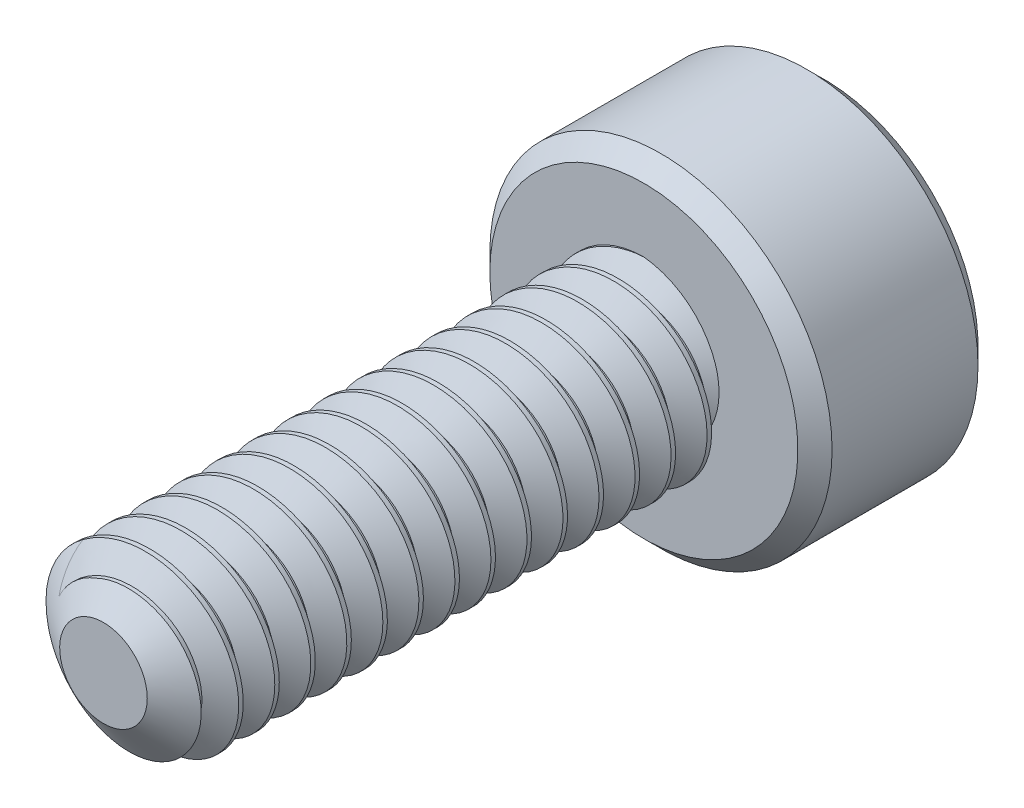
SolidWorks part; units mm, degrees
other "DetailItem1"
ref_plane "Front Plane" through (0, 0, 0) normal (0, 0, 1) x (1, 0, 0)
ref_plane "Top Plane" through (0, 0, 0) normal (0, 1, 0) x (1, 0, 0)
ref_plane "Right Plane" through (0, 0, 0) normal (1, 0, 0) x (0, 0, -1)
sketch "Sketch1" plane through (0, 0, 0) normal (0, 0, 1) x (1, 0, 0)
  circle A0 centre (0, 0) radius 1
  dimension "OD" = 2
extrude "Extrude1" add sketch "Sketch1" against normal blind 6
sketch "Sketch2" plane through (0, 0, 0) normal (0, 0, 1) x (1, 0, 0)
  circle A0 centre (0, 0) radius 1 construction
  circle A1 centre (0, 0) radius 1
curve "Helix/Spiral1" pitch 0.4 height 6.4 radius 1 centre (0, 0, 0) axis (0, 0, -1) start towards (0, 1, 0) parameters "pitch"=0.4
sketch "Sketch3" plane through (0, 0, 0) normal (1, 0, 0) x (0, 0, -1)
  line L0 (-0.35, 1) -> (-0.2, 0.7402)
  line L1 (-0.2, 0.7402) -> (-0.15, 0.7402)
  line L2 (-0.15, 0.7402) -> (0, 1)
  line L3 (-0.35, 1) -> (0, 1)
  line L4 (-0.175, 1) -> (-0.175, 0.7402) construction
  line L5 (-0.275, 0.8701) -> (-0.075, 0.8701) construction
  line L6 (0, 1) -> (0, -1) construction
  dimension "D1" = 0.05
  dimension "D2" = 0.2
  dimension "D3" = 60
sweep "Cut-Sweep1" cut profiles "Sketch3" path "Helix/Spiral1" align with end faces yes
sketch "Sketch4" plane through (0, 0, 0) normal (1, 0, 0) x (0, 0, -1)
  line L0 (0.3598, 1) -> (0, 0.4862)
  line L1 (0, 0.4862) -> (0, 1)
  line L2 (0.3598, 1) -> (0, 1)
  line L3 (-0.35, 1) -> (0, 1) construction
  line L4 (0, 0) -> (7.0209, 0) construction
  dimension "D1" = 55
  dimension "D2" = 0.254
revolve "Cut-Revolve1" cut sketch "Sketch4" angle 360 about L4
sketch "Sketch6" plane through (0, 0, -6) normal (0, 0, -1) x (-1, 0, 0)
  circle A0 centre (0, 0) radius 1.9
  dimension "head dia" = 3.8
extrude "Extrude2" add sketch "Sketch6" along normal blind 2
sketch "Sketch7" plane through (0, 0, -8) normal (0, 0, -1) x (-1, 0, 0)
  line L1 (0, 0.866) -> (-0.75, 0.433)
  line L2 (-0.75, 0.433) -> (-0.75, -0.433)
  line L3 (-0.75, -0.433) -> (0, -0.866)
  line L4 (0, -0.866) -> (0.75, -0.433)
  line L5 (0.75, -0.433) -> (0.75, 0.433)
  line L6 (0.75, 0.433) -> (0, 0.866)
  circle A0 centre (0, 0) radius 0.75 construction
  dimension "hex dia" = 1.5
extrude "Cut-Extrude1" cut sketch "Sketch7" against normal blind 1.125
sketch "Sketch8" plane through (0, 0, -8) normal (0, 0, -1) x (-1, 0, 0)
  circle A0 centre (0, 0) radius 0.866
extrude "Cut-Extrude2" cut sketch "Sketch8" against normal through all draft 45
chamfer "Chamfer1" distance 0.19 angle 45 2 edges at (-1.9, 0, -8) (-1.9, 0, -6)
sketch "Sketch10" plane through (0, 0, -6) normal (0, 0, 1) x (1, 0, 0)
  circle A1 centre (0, 0) radius 1
  circle A2 centre (0, 0) radius 1
  dimension "D1" = 0
ref_plane "Plane1" through (0, 0, 0) normal (0, 0, 1) x (1, 0, 0)
extrude "partial thread" [suppressed] add sketch "Sketch10" along normal up to surface (2 mm away) separate body up to plane "Plane1"
chamfer "Chamfer2" [suppressed] distance 0.04 angle 45
combine bodies "Combine1" [suppressed] operation type add bodies to combine 107 108
sketch "Sketch9" plane through (0, 0, 0) normal (1, 0, 0) x (0, 0, -1)
  line L0 (0, 1) -> (0, -1) construction
  line L1 (1, 1) -> (1, -1) construction
  dimension "D1" = 1
equation "\"D3@Helix/Spiral1\" = \"screw length@Extrude1\"+\"pitch@Helix/Spiral1\""
equation "\"D1@Sketch3\" = \"pitch@Helix/Spiral1\"*.125"
equation "\"D2@Sketch3\" = \"pitch@Helix/Spiral1\"*.5"
equation "\"D1@Cut-Extrude1\" = \"hex dia@Sketch7\"*.75"
equation "\"D1@Chamfer1\" = \"head dia@Sketch6\"*.05"
equation "\"D1@Sketch9\" = \"pitch@Helix/Spiral1\"*2.5"
equation "\"D1@Chamfer2\"=\"OD@Sketch1\"*.02"
